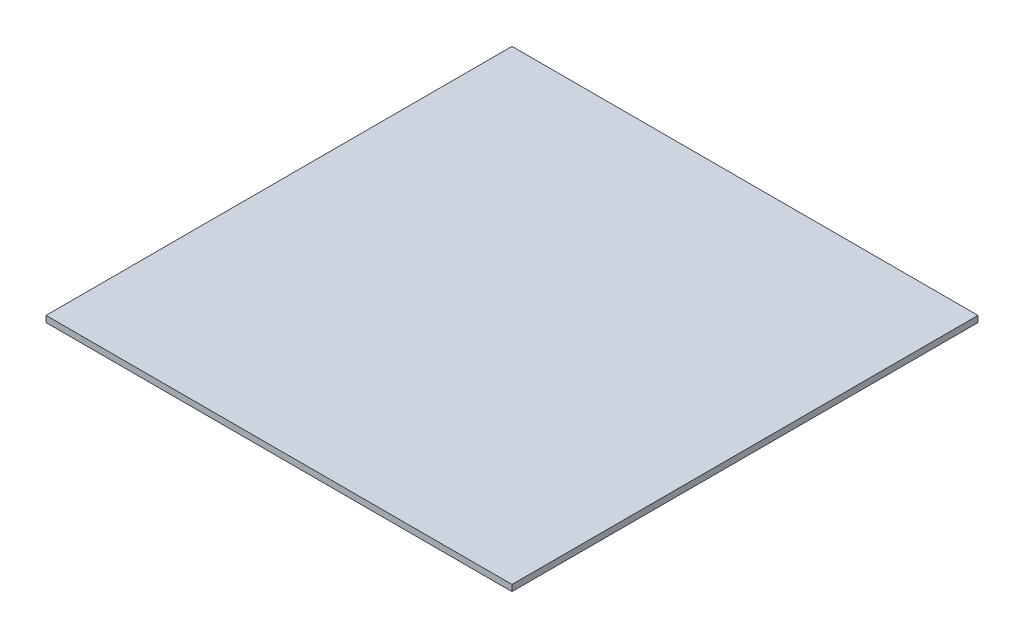
SolidWorks part; units mm, degrees
ref_plane "Front Plane" through (0, 0, 0) normal (0, 0, 1) x (1, 0, 0)
ref_plane "Top Plane" through (0, 0, 0) normal (0, 1, 0) x (1, 0, 0)
ref_plane "Right Plane" through (0, 0, 0) normal (1, 0, 0) x (0, 0, -1)
sketch "Sketch1" plane through (0, 0, 0) normal (0, 1, 0) x (1, 0, 0)
  line L1 (-56.035, 56.035) -> (56.035, 56.035)
  line L2 (-56.035, 56.035) -> (-56.035, -56.035)
  line L3 (-56.035, -56.035) -> (56.035, -56.035)
  line L4 (56.035, 56.035) -> (56.035, -56.035)
  line L5 (-56.035, 56.035) -> (56.035, -56.035) construction
  line L6 (-56.035, -56.035) -> (56.035, 56.035) construction
  point P0 (0, 0)
  dimension "D1" = 112.07
  dimension "D2" = 112.07
extrude "Boss-Extrude1" add sketch "Sketch1" along normal blind 1.5
equation "\"D2@Sketch1\"=\"D1@Sketch1\""
